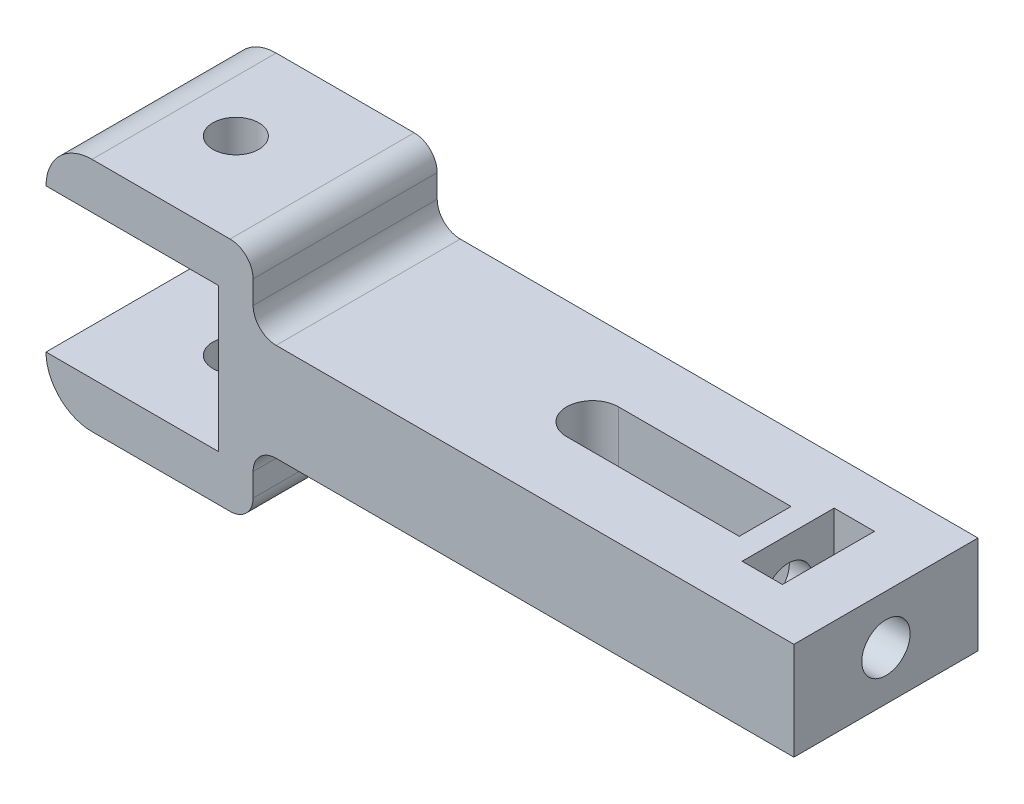
SolidWorks part; units mm, degrees
ref_plane "Front Plane" through (0, 0, 0) normal (0, 0, 1) x (1, 0, 0)
ref_plane "Top Plane" through (0, 0, 0) normal (0, 1, 0) x (1, 0, 0)
ref_plane "Right Plane" through (0, 0, 0) normal (1, 0, 0) x (0, 0, -1)
sketch "Sketch1" plane through (0, 0, 0) normal (0, 0, 1) x (1, 0, 0)
  line L0 (0, 0) -> (-47, 0)
  line L1 (-47, 0) -> (-47, 6)
  line L2 (-47, 6) -> (-65, 6)
  line L3 (-65, 6) -> (-65, 2)
  line L4 (-65, 2) -> (-50, 2)
  line L5 (-50, 2) -> (-50, -10.5)
  line L6 (0, 0) -> (0, -8.5)
  line L7 (0, -4.25) -> (-50, -4.25) construction
  line L8 (-65, -10.5) -> (-50, -10.5)
  line L9 (-65, -14.5) -> (-65, -10.5)
  line L10 (-47, -14.5) -> (-65, -14.5)
  line L11 (-47, -8.5) -> (-47, -14.5)
  line L12 (0, -8.5) -> (-47, -8.5)
  dimension "D1" = 65
  dimension "D2" = 15
  dimension "D3" = 4.25
  dimension "D4" = 6.25
  dimension "D5" = 4
  dimension "D6" = 18
extrude "Boss-Extrude1" add sketch "Sketch1" along normal blind 16
sketch "Sketch2" plane through (0, 0, 0) normal (0, 1, 0) x (1, 0, 0)
  line L0 (0, -8) -> (-47, -8) construction
  line L1 (0, -16) -> (0, 0) construction
  line L2 (-47, -16) -> (-47, 0) construction
  line L4 (-8.5, -4) -> (-5, -4)
  line L5 (-8.5, -4) -> (-8.5, -12)
  line L6 (-8.5, -12) -> (-5, -12)
  line L7 (-5, -4) -> (-5, -12)
  line L8 (-8.5, -4) -> (-5, -12) construction
  line L9 (-8.5, -12) -> (-5, -4) construction
  line L10 (-25.5, -10.25) -> (-10.5, -10.25)
  line L12 (-25.5, -5.75) -> (-10.5, -5.75)
  line L13 (-10.5, -10.25) -> (-10.5, -5.75)
  line L14 (-25.5, -10.25) -> (-10.5, -5.75) construction
  line L15 (-25.5, -5.75) -> (-10.5, -10.25) construction
  arc A0 (-25.5, -5.75) -> (-25.5, -10.25) centre (-25.5, -8) ccw
  point P6 (-6.75, -8)
  point P11 (-18, -8)
  dimension "D7" = 2.25
  dimension "D1" = 8
  dimension "D2" = 3.5
  dimension "D3" = 5
  dimension "D4" = 2
  dimension "D5" = 4.5
  dimension "D6" = 15
extrude "Cut-Extrude1" cut sketch "Sketch2" against normal through all
sketch "Sketch3" plane through (0, 0, 0) normal (1, 0, 0) x (0, 0, -1)
  line L0 (-8, 0) -> (-8, -8.5) construction
  line L1 (-16, 0) -> (0, 0) construction
  line L2 (-16, -8.5) -> (0, -8.5) construction
  circle A0 centre (-8, -4.25) radius 2.1
  dimension "D1" = 4.2
extrude "Cut-Extrude2" cut sketch "Sketch3" against normal up to surface (10.5 mm away) up to face at (-10.5, -4.25, 8)
fillet "Fillet1" radius 2 4 edges at (-47, -8.5, 8) (-47, 6, 8) (-47, 0, 8) (-47, -14.5, 8)
sketch "Sketch4" plane through (0, -10.5, 0) normal (0, 1, 0) x (1, 0, 0)
  line L0 (-65, -8) -> (-49, -8) construction
  line L1 (-65, -16) -> (-65, 0) construction
  line L2 (-49, 0) -> (-49, -16) construction
  circle A0 centre (-57, -8) radius 9
  dimension "D1" = 18
extrude "Cut-Extrude3" cut sketch "Sketch4" along normal up to surface (12.5 mm away) up to face at (-57.5, 2, 8)
sketch "Sketch5" plane through (0, 6, 0) normal (0, 1, 0) x (1, 0, 0)
  line L0 (-65, -8) -> (-49, -8) construction
  line L1 (-65, -16) -> (-65, 0) construction
  line L2 (-49, -16) -> (-49, 0) construction
  circle A0 centre (-56.5, -8) radius 2
  dimension "D1" = 4
  dimension "D2" = 8.5
extrude "Cut-Extrude4" cut sketch "Sketch5" against normal through all
fillet "Fillet2" radius 4 2 edges at (-65, -14.5, 8) (-65, 6, 8)
equation "\"X-ROD-SPACING\"=45"
equation "\"Y-ROD-SPACING\"=75"
equation "\"Z-ROD-SPACING\"=17.5"
equation "\"Y-BED-OFFSET\"=2"
equation "\"Y-BED-ROD-INSET\"=3.5"
equation "\"T-SLOT-NUT-FILLET-RADIUS\"=0.25"
equation "\"T-SLOT-SCREW-SHAFT-RADIUS\"=1.75"
equation "\"T-SLOT-SCREW-SHAFT-CUTOUT-LENGTH\"=10.5"
equation "\"T-SLOT-NUT-DEPTH\"=4.2"
equation "\"T-SLOT-NUT-WIDTH\"=3"
equation "\"T-SLOT-NUT-END-DISTANCE\"=8"
equation "\"ACRYLIC-THICKNESS\"=10"
equation "\"ACRYLIC-TAB-CUTOUT-SIZE\"=\"ACRYLIC-THICKNESS\"+\"ACRYLIC-TAB-TOLERANCE\"*2"
equation "\"ACRYLIC-TAB-WIDTH\"=\"ACRYLIC-THICKNESS\""
equation "\"ACRYLIC-M3-HOLE\"=3.1"
equation "\"SMOOTHROD-CAP-SCREW-DISTANCE\"=20"
equation "\"FRAME-WIDTH-INNER\"=370"
equation "\"NEMA17-HOLE-SPACING\"=31"
equation "\"NEMA17-CENTRAL-CUTOUT\"=22.5"
equation "\"Z-BRACKET-REACH\"=55"
equation "\"TOP-BRACKET-SPACING\"=40"
equation "\"SMOOTHROD-X-LENGTH\"=350"
equation "\"SMOOTHROD-Y-LENGTH\"=350"
equation "\"SMOOTHROD-Z-LENGTH\"=350"
equation "\"SMOOTHROD-TIGHTENING-HEADROOM\"=1"
equation "\"LEADSCREW-Z-LENGTH\"=300"
equation "\"SCREW-HEAD-RADIUS\"=6"
equation "\"PRINTED-X-SMOOTHROD-DIAMETER\"=8.2"
equation "\"PRINTED-X-SMOOTHROD-CUTOUT\"=10"
equation "\"PRINTED-X-BASE-HEIGHT\"=10"
equation "\"PRINTED-LM8UU-CUTOUT-SIZE\"=15.25"
equation "\"PRINTED-LM8UU-CUTOUT-LENGTH\"=24.5"
equation "\"PRINTED-X-IDLER-HEIGHT\"=16"
equation "\"D1@Boss-Extrude1\"=\"PRINTED-X-IDLER-HEIGHT\""
